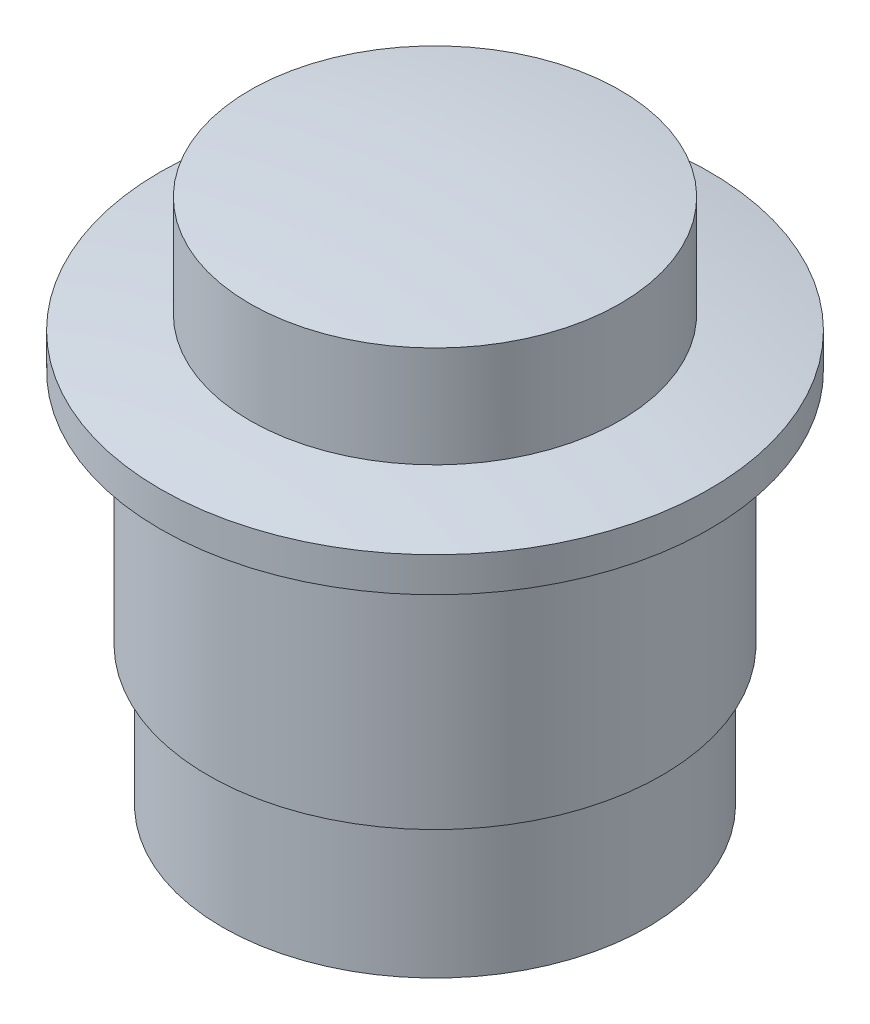
SolidWorks part; units mm, degrees
ref_plane "Front Plane" through (0, 0, 0) normal (0, 0, 1) x (1, 0, 0)
ref_plane "Top Plane" through (0, 0, 0) normal (0, 1, 0) x (1, 0, 0)
ref_plane "Right Plane" through (0, 0, 0) normal (1, 0, 0) x (0, 0, -1)
sketch "Sketch1" plane through (0, 0, 0) normal (0, 1, 0) x (1, 0, 0)
  circle A0 centre (0, 0) radius 7.35
  dimension "D1" = 14.7
extrude "Boss-Extrude1" add sketch "Sketch1" along normal blind 4.8
sketch "Sketch2" plane through (0, 4.8, 0) normal (0, 1, 0) x (1, 0, 0)
  circle A0 centre (0, 0) radius 7.85
  dimension "D1" = 15.7
extrude "Boss-Extrude2" add sketch "Sketch2" along normal offset from surface (8.2 mm away) 13
sketch "Sketch3" plane through (0, 0, 0) normal (0, 0, 1) x (1, 0, 0)
  line L0 (-7.85, 13) -> (-9.5, 13)
  line L1 (-9.5, 13) -> (-9.5, 14.2)
  line L2 (0, 15.2009) -> (0, -2.1066) construction
  line L3 (-6.4, 14.6995) -> (-6.4, 18.1995)
  line L4 (0, 18.6108) -> (0, 13)
  line L5 (7.85, 13) -> (-7.85, 13) construction
  line L6 (0, 13) -> (-7.85, 13)
  arc A0 (-6.4, 14.6995) -> (-9.5, 14.2) centre (0, -34.8892) ccw
  arc A1 (0, 18.6108) -> (-6.4, 18.1995) centre (0, -31.3892) ccw
  arc A2 (-49.9694, -33.1392) -> (49.9694, -33.1392) centre (0, -31.3892) ccw
  arc A3 (-49.9694, -33.1392) -> (49.9694, -33.1392) centre (0, -34.8892) ccw
  dimension "D3" = 100
  dimension "D1" = 19
  dimension "D2" = 1.2
  dimension "D4" = 12.8
  dimension "D5" = 3.5
revolve "Revolve2" add sketch "Sketch3" angle 360 about L2 region at (-3.7, 15.5089, 0)
